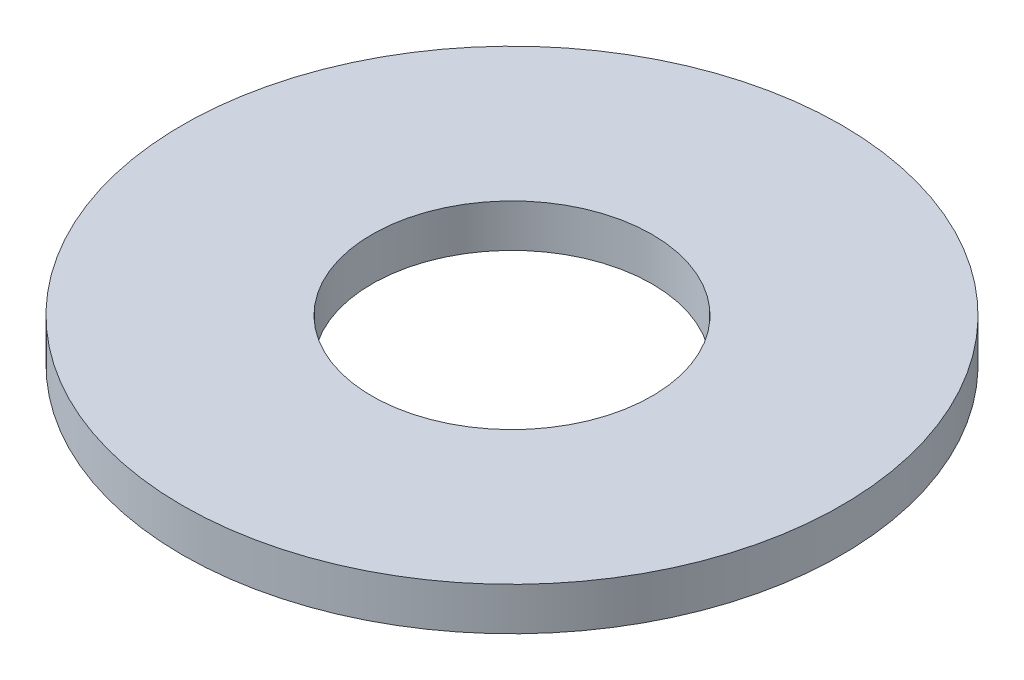
SolidWorks part; units mm, degrees
ref_plane "Front Plane" through (0, 0, 0) normal (0, 0, 1) x (1, 0, 0)
ref_plane "Top Plane" through (0, 0, 0) normal (0, 1, 0) x (1, 0, 0)
ref_plane "Right Plane" through (0, 0, 0) normal (1, 0, 0) x (0, 0, -1)
sketch "Sketch1" plane through (0, 0, 0) normal (0, 1, 0) x (1, 0, 0)
  circle A0 centre (0, 0) radius 100
  dimension "FLANGE_OD" = 200
extrude "Boss-Extrude1" add sketch "Sketch1" along normal blind 13
sketch "Sketch2" plane through (0, 0, 0) normal (0, 1, 0) x (1, 0, 0)
  circle A0 centre (0, 0) radius 42.5
  dimension "BORE_D" = 85
extrude "Cut-Extrude1" cut sketch "Sketch2" along normal through all
sketch "Sketch3" plane through (0, 13, 0) normal (0, 1, 0) x (1, 0, 0)
  circle A0 centre (0, 0) radius 33.2251 construction
  circle A1 centre (-33.2251, 0) radius 3.5064
  dimension "BOLT_D" = 7.0128
  dimension "BOLT_PCD" = 66.4503
extrude "Cut-Extrude2" cut sketch "Sketch3" against normal blind 11.2963 rebuild error yes
pattern_circular "CirPattern1" count 8 over 360 rebuild error yes
